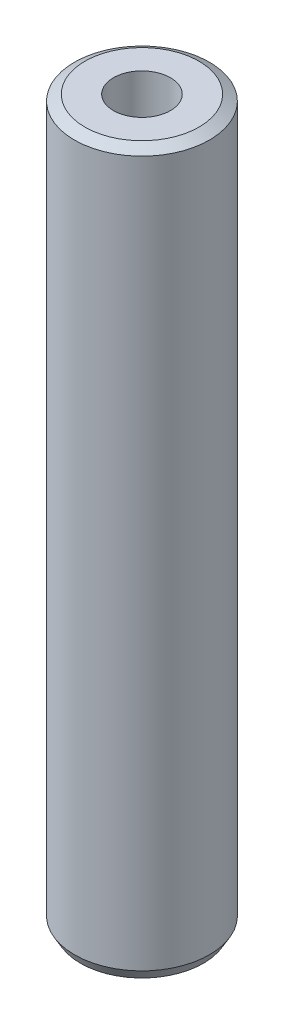
SolidWorks part; units mm, degrees
ref_plane "Front Plane" through (0, 0, 0) normal (0, 0, 1) x (1, 0, 0)
ref_plane "Top Plane" through (0, 0, 0) normal (0, 1, 0) x (1, 0, 0)
ref_plane "Right Plane" through (0, 0, 0) normal (1, 0, 0) x (0, 0, -1)
sketch "Sketch1" plane through (0, 0, 0) normal (0, 1, 0) x (1, 0, 0)
  circle A0 centre (0, 0) radius 27.5
  dimension "SHAFT_OD" = 55
extrude "Boss-Extrude1" add sketch "Sketch1" along normal blind 294.1689
sketch "Sketch2" plane through (0, 0, 0) normal (0, 1, 0) x (1, 0, 0)
  circle A0 centre (0, 0) radius 11.6192
  dimension "BORE_D" = 23.2384
extrude "Cut-Extrude1" cut sketch "Sketch2" along normal through all
chamfer "Chamfer1" distance 2.452 angle 60 2 edges at (0, 294.1689, 27.5) (0, 0, 27.5) first distance on face at (0, 294.1689, 27.5) first distance on face at (0, 0, 11.6192)
